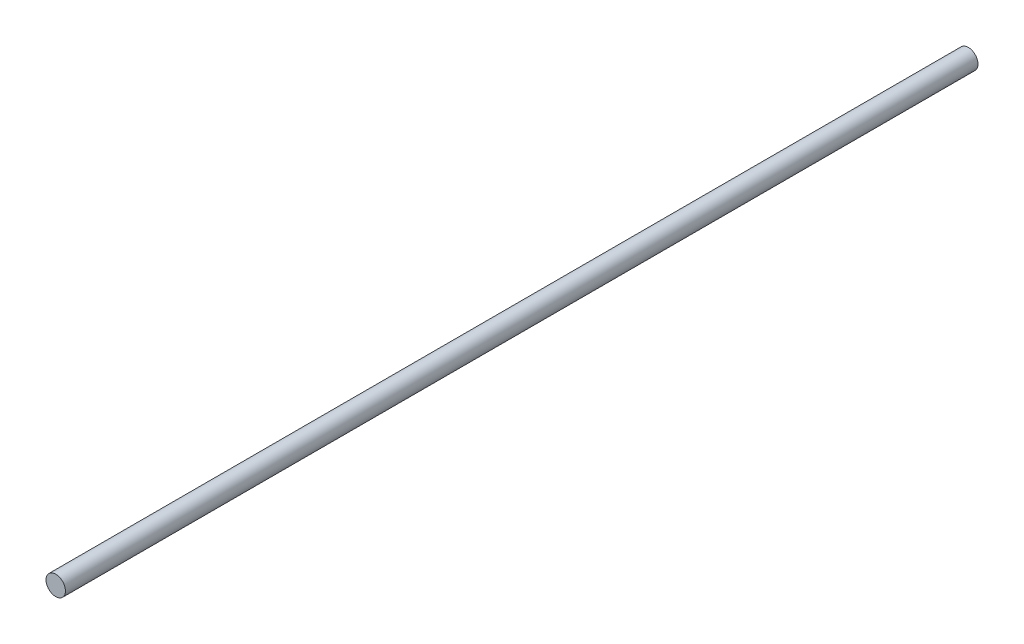
SolidWorks part; units mm, degrees
material "AISI 316 Stainless Steel Sheet (SS)"
ref_plane "Front (1)" through (0, 0, 0) normal (0, 0, 1) x (1, 0, 0)
ref_plane "Top (2)" through (0, 0, 0) normal (0, 1, 0) x (1, 0, 0)
ref_plane "Right (3)" through (0, 0, 0) normal (1, 0, 0) x (0, 0, -1)
ref_axis "X Axis" through (13.5064, 0, 0) along (-1, 0, 0)
ref_axis "Y Axis" through (0, 12.3593, 0) along (0, -1, 0)
ref_axis "Z Axis" through (0, 0, 14.1119) along (0, 0, -1)
sketch "Sketch2" plane through (0, 0, 0) normal (1, 0, 0) x (0, 0, -1)
  line L1 (0, 0) -> (375, 0)
  line L2 (0, 0) -> (0, 4)
  line L3 (0, 4) -> (375, 4)
  line L4 (375, 0) -> (375, 4)
  dimension "D1" = 375
  dimension "D2" = 4
revolve "Revolve1" add sketch "Sketch2" angle 360 about L1
cosmetic thread "Cosmetic Thread2" parameters "D2"=6.891
